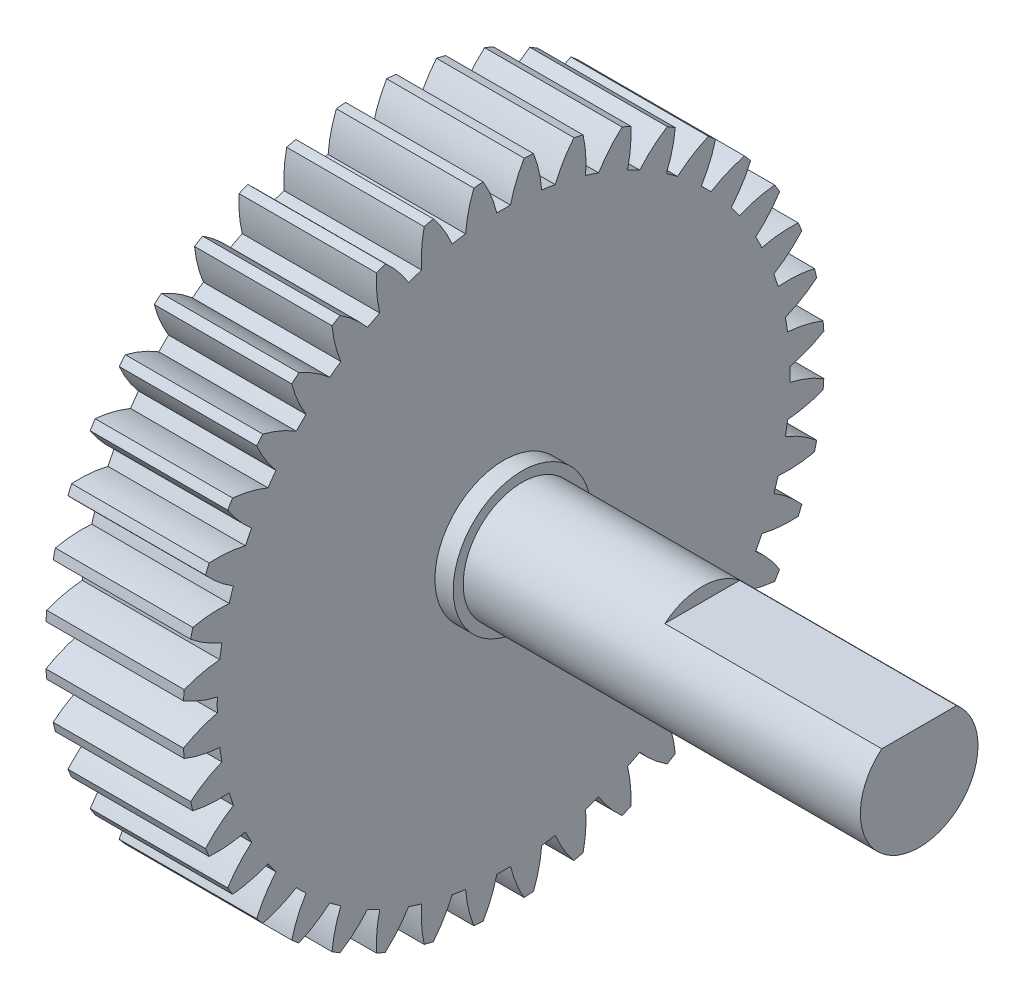
SolidWorks part; units mm, degrees
ref_plane "Plane1" through (0, 0, 0) normal (0, 0, 1) x (1, 0, 0)
ref_plane "Plane2" through (0, 0, 0) normal (0, 1, 0) x (1, 0, 0)
ref_plane "Plane3" through (0, 0, 0) normal (1, 0, 0) x (0, 0, -1)
sketch "HoldingSke" plane through (0, 0, 0) normal (0, 1, 0) x (1, 0, 0)
  line L0 (0, 0) -> (0.766, -0.6428)
  line L1 (-15, 0) -> (100, 0) construction
  line L2 (0, 0) -> (-2.1039, 2.3779)
  line L3 (0, 0) -> (-11.863, 4.5341)
  line L4 (0, 0) -> (6.6156, 5.5511)
  line L5 (0, 0) -> (-46.8476, -17.4728)
  line L6 (0, 0) -> (-7.4607, -5.0337)
  line L7 (-2.1039, 2.3779) -> (8.6586, 51.2059)
  line L8 (-76.2, 54.61) -> (-75.5, 54.61)
  line L9 (-71.009, 38.7566) -> (-53.1078, 45.2721)
  line L10 (-76.2, 71.12) -> (104.1128, 71.12)
  line L11 (0, 0) -> (-9, 0)
  line L12 (-76.2, 101.6) -> (-76.162, 101.6)
  line L13 (24.9733, 27.94) -> (52.9518, 28.4284)
  line L14 (24.9733, 27.94) -> (24.9743, 27.94)
  line L15 (24.9733, 27.94) -> (100.4006, 29.5858)
  line L16 (-63.627, -1) -> (-12.827, -1)
  circle A0 centre (0, 0) radius 2
  circle A1 centre (0, 0) radius 18.749
  circle A2 centre (0, 0) radius 37.5
  circle A3 centre (0, 0) radius 2
  dimension "MHD" = 37.498
  dimension "Hub_dia" = 75
  dimension "Bore" = 4
  dimension "MBD" = 4
  dimension "Num_teeth" = 40
  dimension "Pitch" = 1
  dimension "Overall_len" = 50
  dimension "Show_teeth" = 40
  dimension "Thickness" = 9
  dimension "OAL" = 50.0001
  dimension "T_dim" = 0.7
  dimension "Ap" = 20
  dimension "H" = 19.05
  dimension "Pitch_radius" = 180.3128
  dimension "Width" = 9
  dimension "Backlash" = 0.038
  dimension "Addendum_fac" = 1
  dimension "Dedendum_fac" = 1.25
  dimension "Clearance_fac" = 0.25
  dimension "Dedendum_add" = 0.001
  dimension "Module" = 1
sketch "BasProSke" plane through (0, 0, 0) normal (0, 1, 0) x (1, 0, 0)
  line L0 (-10, 0) -> (60, 0) construction
  line L1 (0, 0) -> (0, 21)
  line L2 (0, 0) -> (9, 0)
  line L3 (9, 0) -> (9, 21)
  line L4 (9, 21) -> (0, 21)
  dimension "Thickness" = 9
  dimension "Diameter" = 42
revolve "Base-Revolve" add sketch "BasProSke" angle 360 about L0
sketch "TooCutSke" plane through (0, 0, 0) normal (1, 0, 0) x (0, 0, -1)
  line L1 (0, 0) -> (0, 107) construction
  line L2 (0, 0) -> (-0.8517, 19.9819) construction
  line L3 (0, 0) -> (-3.1363, 39.8509) construction
  line L4 (-0.8517, 19.9819) -> (-1.5682, 19.9255) construction
  arc A0 (0.4487, 18.7436) -> (-0.4487, 18.7436) centre (0, 0) ccw
  arc A1 (1.3547, 20.9817) -> (-1.3547, 20.9817) centre (0, 0) ccw
  circle A2 centre (0, 0) radius 20 construction
  circle A3 centre (0, 0) radius 18.7939 construction
  arc A4 (-0.4487, 18.7436) -> (-1.3547, 20.9817) centre (-8.2322, 16.895) ccw
  arc A5 (1.3547, 20.9817) -> (0.4487, 18.7436) centre (8.2322, 16.895) ccw
  dimension "Root_dia" = 37.498
  dimension "Overcut_dia" = 42.0508
  dimension "Pitch_dia" = 40
  dimension "Base_dia" = 37.5877
  dimension "Flank_rad" = 8
  dimension "Half_ang" = 4.5
  dimension "Half_CT" = 0.7187
extrude "ToothCut" cut sketch "TooCutSke" along normal through all
fillet "Breaks" [suppressed] radius 0.02 tangent propagation no
fillet "RootFillets" [suppressed] radius 0.251
pattern_circular "TeethCuts" count 40 every 9 about axis through (-10, 0, 0) along (1, 0, 0) of "ToothCut", "RootFillets", "Breaks"
sketch "HubNeaOneSke" plane through (0, 0, 0) normal (-1, 0, 0) x (0, 0, 1)
  circle A0 centre (0, 0) radius 18.749
  dimension "Diameter" = 37.498
extrude "HubNearOne" [suppressed] add sketch "HubNeaOneSke" along normal blind 41.0001
sketch "HubNeaBotSke" plane through (0, 0, 0) normal (-1, 0, 0) x (0, 0, 1)
  circle A0 centre (0, 0) radius 18.749
  dimension "Diameter" = 37.498
extrude "HubNearBoth" [suppressed] add sketch "HubNeaBotSke" along normal blind 20.5
ref_plane "FarPln" through (9, 0, 0) normal (1, 0, 0) x (0, 0, -1)
sketch "HubFarSke" plane through (9, 0, 0) normal (1, 0, 0) x (0, 0, -1)
  circle A0 centre (0, 0) radius 18.749
  dimension "Diameter" = 37.498
extrude "HubFar" [suppressed] add sketch "HubFarSke" along normal blind 20.5
sketch "BorSke" plane through (0, 0, 0) normal (1, 0, 0) x (0, 0, -1)
  circle A0 centre (0, 0) radius 2
  dimension "Diameter" = 4
extrude "Bore" cut sketch "BorSke" along normal mid plane 100.0001
sketch "KeySke" plane through (0, 0, 0) normal (1, 0, 0) x (0, 0, -1)
  line L0 (-0.8, 0) -> (-0.8, 2.7)
  line L1 (-0.8, 2.7) -> (0.8, 2.7)
  line L2 (0.8, 2.7) -> (0.8, 0)
  line L3 (0, 0) -> (0, 34) construction
  line L4 (-0.8, 0) -> (0.8, 0)
  dimension "Offset" = 2.7
  dimension "Width" = 1.6
extrude "Keyway" [suppressed] cut sketch "KeySke" along normal mid plane 100.0001
pattern_circular "Keyway2" [suppressed] count 2 every 90 about axis through (-10, 0, 0) along (1, 0, 0) reverse direction yes
sketch "Sketch1" plane through (9, 0, 0) normal (1, 0, 0) x (0, 0, -1)
  line L0 (-2.45, 2.9698) -> (2.45, 2.9698)
  circle A0 centre (0, 0) radius 4.5
  circle A1 centre (0, 0) radius 3.85
  dimension "D1" = 4.9
  dimension "D2" = 7.7
  dimension "D3" = 9
extrude "Boss-Extrude1" add sketch "Sketch1" along normal blind 27.2 and the other way blind 9 contours L0 A1 region at (9, -0.2248, 0)
extrude "Boss-Extrude2" add sketch "Sketch1<3>" along normal blind 13 and the other way blind 9 contours L0 A1 region at (9, 3.3256, 0)
sketch "Sketch1<3>" plane through (9, 0, 0) normal (1, 0, 0) x (0, 0, -1) same geometry as "Sketch1"
extrude "Boss-Extrude3" add sketch "Sketch1<4>" along normal blind 1.2 contours A0 A1 region at (9, 0, 4.3727)
sketch "Sketch1<4>" plane through (9, 0, 0) normal (1, 0, 0) x (0, 0, -1) same geometry as "Sketch1"
equation "' \"Module@HoldingSke\" = 6.35"
equation "' \"Num_teeth@HoldingSke\" = 12"
equation "' \"Ap@HoldingSke\" =  20"
equation "' \"Ap@HoldingSke\" = 20"
equation "' \"Width@HoldingSke\" = 0.5 * 25.4"
equation "' \"Hub_dia@HoldingSke\"= 1 * 25.4"
equation "' \"Hub_dia@HoldingSke\" = 1 * 25.4"
equation "' \"Overall_len@HoldingSke\" = 1.0 * 25.4"
equation "' \"Bore@HoldingSke\" = 0.75 * 25.4"
equation "' \"T_dim@HoldingSke\" = 0.1 * 25.4"
equation "' \"Width@KeySke\" = 0.25 * 25.4"
equation "' \"Show_teeth@HoldingSke\" = 13"
equation "' \"Backlash@HoldingSke\" = 0.009 * 25.4"
equation "' \"Addendum_fac@HoldingSke\" = 1.0"
equation "' \"Dedendum_fac@HoldingSke\" = 1.25"
equation "' \"Dedendum_add@HoldingSke\" = 0.00005 * 25.4"
equation "' \"Clearance_fac@HoldingSke\" = 0.25"
equation "\"Pitch@HoldingSke\" = 1 / \"Module@HoldingSke\""
equation "\"Overcut_dia@TooCutSke\" = (\"Num_teeth@HoldingSke\" + 2 * \"Addendum_fac@HoldingSke\") / \"Pitch@HoldingSke\" + 0.002 * 25.4"
equation "\"Pitch_dia@TooCutSke\" = \"Num_teeth@HoldingSke\" / \"Pitch@HoldingSke\""
equation "\"Base_dia@TooCutSke\" = \"Num_teeth@HoldingSke\" / \"Pitch@HoldingSke\" * cos((\"Ap@HoldingSke\"  * 3.14159265 / 180))"
equation "\"Root_dia@TooCutSke\" = (\"Num_teeth@HoldingSke\" + 2) / \"Pitch@HoldingSke\" - 2 * (\"Addendum_fac@HoldingSke\" + \"Dedendum_fac@HoldingSke\") / \"Pitch@HoldingSke\" - \"Dedendum_add@HoldingSke\" * 2"
equation "\"Half_ang@TooCutSke\" = 180 / \"Num_teeth@HoldingSke\""
equation "\"Half_CT@TooCutSke\" = \"Num_teeth@HoldingSke\" / \"Pitch@HoldingSke\" * sin((3.14159265 / 2 / \"Num_teeth@HoldingSke\")) / 2 - 7 * \"Backlash@HoldingSke\" / 4"
equation "\"Flank_rad@TooCutSke\" = \"Num_teeth@HoldingSke\" / \"Pitch@HoldingSke\" / 5"
equation "\"Radius@RootFillets\" = \"Clearance_fac@HoldingSke\" / \"Pitch@HoldingSke\" + \"Dedendum_add@HoldingSke\""
equation "\"Break_rad@Breaks\" = 0.02 / \"Pitch@HoldingSke\""
equation "\"Thickness@HoldingSke\" = \"Width@HoldingSke\""
equation "\"OAL@HoldingSke\" = \"Thickness@HoldingSke\""
equation "\"MHD@HoldingSke\" = (\"Num_teeth@HoldingSke\" + 2) / \"Pitch@HoldingSke\" - 2 * (\"Addendum_fac@HoldingSke\" + \"Dedendum_fac@HoldingSke\")  / \"Pitch@HoldingSke\" - \"Dedendum_add@HoldingSke\" * 2"
equation "\"MBD@HoldingSke\" = (\"Num_teeth@HoldingSke\" + 2) / \"Pitch@HoldingSke\" - 2 * (\"Addendum_fac@HoldingSke\" + \"Dedendum_fac@HoldingSke\")  / \"Pitch@HoldingSke\" - \"Dedendum_add@HoldingSke\" * 2 - 0.002 * 25.4"
equation "\"MHD@HoldingSke\" = ((sgn( \"MHD@HoldingSke\" - \"Hub_dia@HoldingSke\" )-1)*( \"MHD@HoldingSke\" - \"Hub_dia@HoldingSke\" ))/-2+ \"Hub_dia@HoldingSke\""
equation "\"MBD@HoldingSke\" = ((sgn( \"MBD@HoldingSke\" - \"Bore@HoldingSke\" )-1)*( \"MBD@HoldingSke\" - \"Bore@HoldingSke\" ))/-2+ \"Bore@HoldingSke\""
equation "\"OAL@HoldingSke\" = ((sgn( \"OAL@HoldingSke\" - \"Overall_len@HoldingSke\" )+1)*( \"OAL@HoldingSke\" - \"Overall_len@HoldingSke\" ))/2 + \"Overall_len@HoldingSke\" + 0.000002 * 25.4"
equation "\"Num_teeth@TeethCuts\" = int( \"Show_teeth@HoldingSke\" ) + 1"
equation "\"Num_teeth@TeethCuts\" = ((sgn( \"Num_teeth@TeethCuts\" - \"Num_teeth@HoldingSke\" )-1)*( \"Num_teeth@TeethCuts\" - \"Num_teeth@HoldingSke\" ))/-2+ \"Num_teeth@HoldingSke\""
equation "\"Num_teeth@TeethCuts\" = ((sgn( \"Num_teeth@TeethCuts\" - 2.0)+1)*( \"Num_teeth@TeethCuts\" - 2.0))/2 +2.0"
equation "\"Angle@TeethCuts\" = 360.0 / \"Num_teeth@HoldingSke\""
equation "\"Diameter@BasProSke\" = (\"Num_teeth@HoldingSke\" + 2 * \"Addendum_fac@HoldingSke\") / \"Pitch@HoldingSke\""
equation "\"Thickness@BasProSke\"  = \"Thickness@HoldingSke\""
equation "' \"Fillet_rad@BasProSke\" =  \"Thickness@HoldingSke\" * 0.05"
equation "' \"Fillet_rad@BasProSke\" = \"Thickness@HoldingSke\" * 0.05"
equation "\"MHD@HoldingSke\" = ((sgn( \"MHD@HoldingSke\" - \"Root_dia@TooCutSke\" )-1)*( \"MHD@HoldingSke\" - \"Root_dia@TooCutSke\" ))/-2+ \"Root_dia@TooCutSke\""
equation "\"Diameter@HubNeaOneSke\" = \"MHD@HoldingSke\""
equation "\"Length@HubNearOne\" = \"OAL@HoldingSke\" - \"Thickness@BasProSke\""
equation "\"Diameter@HubNeaBotSke\" = \"MHD@HoldingSke\""
equation "\"Length@HubNearBoth\" = ( \"OAL@HoldingSke\" - \"Thickness@BasProSke\" ) / 2.0"
equation "\"Thickness@FarPln\" = \"Thickness@BasProSke\""
equation "\"Diameter@HubFarSke\" = \"MHD@HoldingSke\""
equation "\"Length@HubFar\" = ( \"OAL@HoldingSke\" - \"Thickness@BasProSke\" ) / 2.0"
equation "\"Diameter@BorSke\" = \"MBD@HoldingSke\""
equation "\"D1@Bore\" = \"OAL@HoldingSke\" * 2.0"
equation "\"D1@Keyway\" = \"OAL@HoldingSke\" * 2.0"
equation "\"Offset@KeySke\" = \"T_dim@HoldingSke\" + \"MBD@HoldingSke\" / 2.0"
